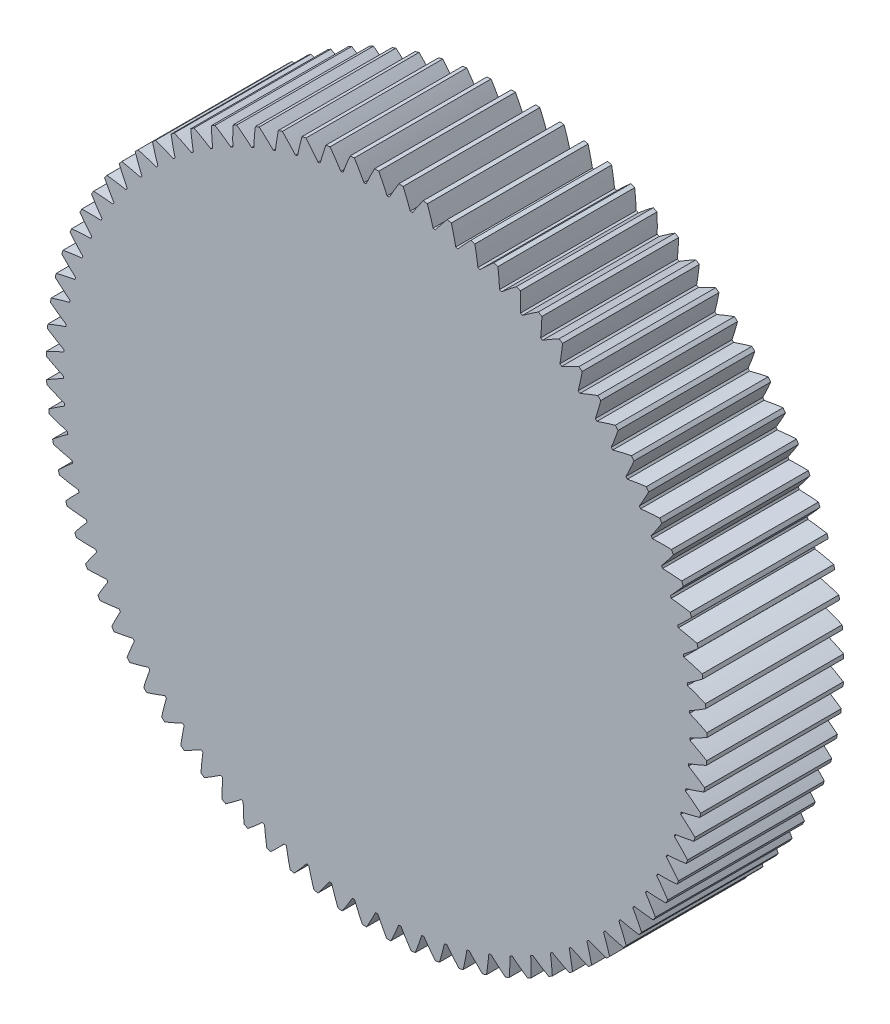
SolidWorks part; units mm, degrees
ref_plane "Front" through (0, 0, 0) normal (0, 0, 1) x (1, 0, 0)
ref_plane "Top" through (0, 0, 0) normal (0, 1, 0) x (1, 0, 0)
ref_plane "Right" through (0, 0, 0) normal (1, 0, 0) x (0, 0, -1)
sketch "Sketch1" plane through (0, 0, 0) normal (0, 0, 1) x (1, 0, 0)
  circle A0 centre (0, 0) radius 412.5
  dimension "D1" = 825
extrude "Base-Extrude" add sketch "Sketch1" against normal blind 180
sketch "Sketch2" plane through (0, 0, 0) normal (0, 0, 1) x (1, 0, 0)
  line L0 (0, 0) -> (0, 64.7411) construction
  line L1 (-7.854, 424.9274) -> (7.854, 424.9274) construction
  line L2 (-13.771, 412.2701) -> (13.771, 412.2701)
  circle A0 centre (0, 0) radius 412.5 construction
  arc A1 (-13.771, 412.2701) -> (-2.7344, 434.9914) centre (332.8356, 257.9502) cw
  arc A2 (2.7344, 434.9914) -> (-2.7344, 434.9914) centre (0, 0) ccw
  arc A3 (13.771, 412.2701) -> (2.7344, 434.9914) centre (-332.8356, 257.9502) ccw
  circle A4 centre (0, 0) radius 425 construction
  dimension "D1" = 850
  dimension "D2" = 870
  dimension "D3" = 2.7344
  dimension "D4" = 7.854
  dimension "D5" = 13.771
extrude "Boss-Extrude1" add sketch "Sketch2" against normal up to surface (180 mm away) up to face at (412.5, 0, -180)
ref_axis "Axis1" through (0, 0, -189) along (0, 0, 1)
pattern_circular "CirPattern1" count 85 every 4.235 about axis through (0, 0, -189) along (0, 0, 1) of "Boss-Extrude1"
ref_plane "Plane1" through (510, 0, 0) normal (1, 0, 0) x (0, 0, -1)
ref_axis "AxisDistance" through (510, 0, 9) along (0, 0, -1)
ref_plane "MidPlane" through (0, 0, -90) normal (0, 0, 1) x (1, 0, 0)
equation "\"D2@CirPattern1\" = 360/\"D1@CirPattern1\""
equation "\"D1@MidPlane\"=\"D1@Base-Extrude\"/2"
